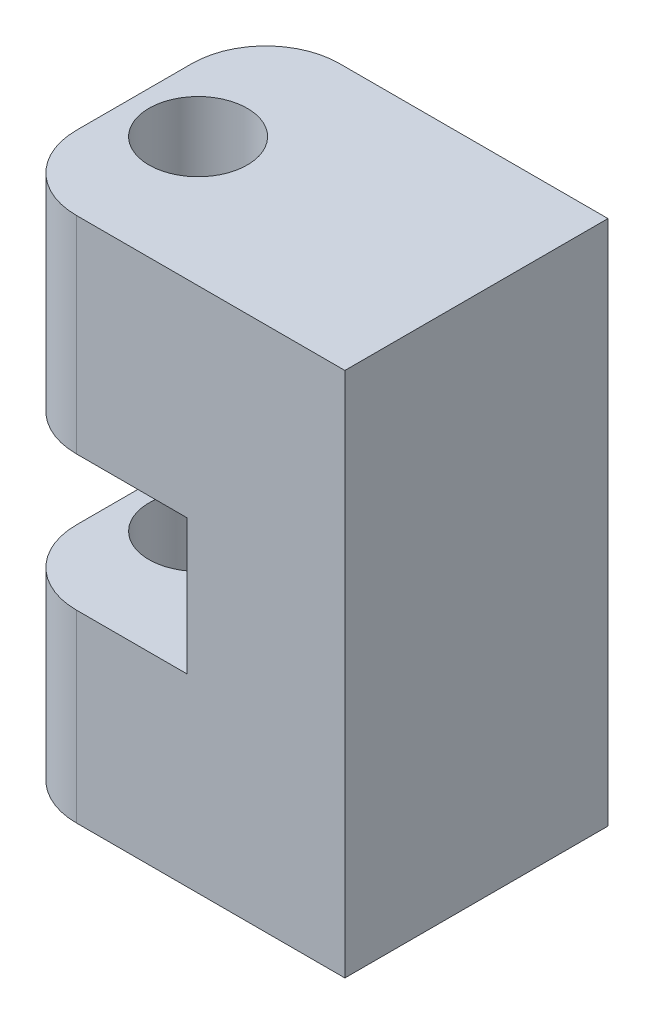
SolidWorks part; units mm, degrees
ref_plane "Front" through (0, 0, 0) normal (0, 0, 1) x (1, 0, 0)
ref_plane "Top" through (0, 0, 0) normal (0, 1, 0) x (1, 0, 0)
ref_plane "Right" through (0, 0, 0) normal (1, 0, 0) x (0, 0, -1)
sketch "Sketch1" plane through (0, 0, 0) normal (0, 1, 0) x (1, 0, 0)
  line L0 (0, 9.3172) -> (0, 9.1678) construction
  line L1 (0, 0) -> (20.32, 0)
  line L2 (0, 0) -> (0, 12.7)
  line L3 (0, 12.7) -> (20.32, 12.7)
  line L4 (20.32, 0) -> (20.32, 12.7)
  line L5 (0.0894, 9.3172) -> (0.0894, 9.1678)
  line L6 (-0.0894, 9.3172) -> (-0.0894, 9.1678)
  line L7 (0, 7.6957) -> (0, 5.0493) construction
  line L10 (5.1, 7.6957) -> (5.1, 5.0493)
  line L11 (-5.1, 7.6957) -> (-5.1, 5.0493)
  arc A0 (0.0894, 9.3172) -> (-0.0894, 9.3172) centre (0, 9.3172) ccw
  arc A1 (-0.0894, 9.1678) -> (0.0894, 9.1678) centre (0, 9.1678) ccw
  arc A4 (5.1, 7.6957) -> (-5.1, 7.6957) centre (0, 7.6957) ccw
  arc A5 (-5.1, 5.0493) -> (5.1, 5.0493) centre (0, 5.0493) ccw
  point P7 (0, 9.2425)
  point P14 (0, 6.3725)
  dimension "D1" = 20.32
  dimension "D2" = 12.7
extrude "Boss-Extrude4" add sketch "Sketch1" along normal blind 25.4 contours L11 A5 L1 L2 A1 L6 A0 L3 A4 | L1 A5 L10 A4 L3 L2 A0 L5 A1 | A5 L1 L4 L3 A4 L10 region at (2.2644, 0, -6.3666) region at (-2.2571, 0, -6.3757) region at (12.2627, 0, -6.3452)
sketch "Sketch3" plane through (0, 25.4, 0) normal (0, 1, 0) x (1, 0, 0)
  circle A0 centre (0, 6.1634) radius 2
  dimension "D1" = 4
extrude "Cut-Extrude1" cut sketch "Sketch3" against normal blind 25.4 contours A0
sketch "Sketch5" plane through (20.32, 0, 0) normal (1, 0, 0) x (0, 0, -1)
  line L1 (38.2751, 38.8271) -> (-16.024, 38.8271)
  line L2 (38.2751, 38.8271) -> (38.2751, -55.3885)
  line L3 (38.2751, -55.3885) -> (-16.024, -55.3885)
  line L4 (-16.024, 38.8271) -> (-16.024, -55.3885)
extrude "Cut-Extrude2" cut sketch "Sketch5" against normal blind 4.5
sketch "Sketch7" plane through (-5.1, 0, 0) normal (-1, 0, 0) x (0, 0, 1)
  line L0 (-7.6957, 25.4) -> (-5.0493, 25.4) construction
  line L1 (-15.6651, 15) -> (3.0281, 15)
  line L2 (-15.6651, 15) -> (-15.6651, 9.5)
  line L3 (-15.6651, 9.5) -> (3.0281, 9.5)
  line L4 (3.0281, 15) -> (3.0281, 9.5)
  dimension "D1" = 5.5
  dimension "D2" = 10.4
extrude "Cut-Extrude3" cut sketch "Sketch7" against normal blind 14.5
sketch "Sketch9" plane through (0, 0, -12.7) normal (0, 0, -1) x (-1, 0, 0)
  line L1 (-22.5674, 28.7595) -> (13.5442, 28.7595)
  line L2 (-22.5674, 28.7595) -> (-22.5674, -4.4046)
  line L3 (-22.5674, -4.4046) -> (13.5442, -4.4046)
  line L4 (13.5442, 28.7595) -> (13.5442, -4.4046)
extrude "Cut-Extrude4" cut sketch "Sketch9" against normal blind 1
sketch "Sketch10" plane through (0, 0, 0) normal (0, 0, 1) x (1, 0, 0)
  line L1 (-28.2632, -7.6451) -> (34.5285, -7.6451)
  line L2 (-28.2632, -7.6451) -> (-28.2632, 29.5981)
  line L3 (-28.2632, 29.5981) -> (34.5285, 29.5981)
  line L4 (34.5285, -7.6451) -> (34.5285, 29.5981)
extrude "Cut-Extrude6" cut sketch "Sketch10" against normal blind 1
fillet "Fillet2" radius 3 4 edges at (-3.1005, 4.75, -1) (-3.1005, 20.2, -1) (-3.1585, 20.2, -11.7) (-3.1585, 4.75, -11.7)
sketch "Sketch11" plane through (9.4, 0, 0) normal (-1, 0, 0) x (0, 0, 1)
  line L1 (-11.7, 9.5) -> (-1, 9.5)
  line L2 (-11.7, 9.5) -> (-11.7, 15)
  line L3 (-11.7, 15) -> (-1, 15)
  line L4 (-1, 9.5) -> (-1, 15)
extrude "Boss-Extrude5" add sketch "Sketch11" along normal blind 2
sketch "Sketch12" plane through (-5.1, 0, 0) normal (-1, 0, 0) x (0, 0, 1)
  line L1 (-13.4183, -11.6019) -> (0, -11.6019)
  line L2 (-13.4183, -11.6019) -> (-13.4183, 44.9502)
  line L3 (-13.4183, 44.9502) -> (0, 44.9502)
  line L4 (0, -11.6019) -> (0, 44.9502)
extrude "Cut-Extrude7" cut sketch "Sketch12" against normal blind 10
sketch "Sketch14" plane through (7.4, 0, 0) normal (-1, 0, 0) x (0, 0, 1)
  line L1 (-11.7, 9.5) -> (-1, 9.5)
  line L2 (-11.7, 9.5) -> (-11.7, 15)
  line L3 (-11.7, 15) -> (-1, 15)
  line L4 (-1, 9.5) -> (-1, 15)
extrude "Boss-Extrude7" add sketch "Sketch14" along normal blind 2
sketch "Sketch15" plane through (4.9, 0, 0) normal (-1, 0, 0) x (0, 0, 1)
  line L1 (-11.7, 0) -> (-1, 0)
  line L2 (-11.7, 0) -> (-11.7, 9.5)
  line L3 (-11.7, 9.5) -> (-1, 9.5)
  line L4 (-1, 0) -> (-1, 9.5)
extrude "Boss-Extrude8" add sketch "Sketch15" along normal blind 6
sketch "Sketch16" plane through (4.9, 0, 0) normal (-1, 0, 0) x (0, 0, 1)
  line L1 (-11.7, 15) -> (-1, 15)
  line L2 (-11.7, 15) -> (-11.7, 25.4)
  line L3 (-11.7, 25.4) -> (-1, 25.4)
  line L4 (-1, 15) -> (-1, 25.4)
extrude "Boss-Extrude9" add sketch "Sketch16" along normal blind 6
fillet "Fillet3" radius 3 4 edges at (-1.1, 20.2, -1) (-1.1, 20.2, -11.7) (-1.1, 4.75, -11.7) (-1.1, 4.75, -1)
sketch "Sketch18" plane through (5.4, 0, 0) normal (-1, 0, 0) x (0, 0, 1)
  line L1 (-11.7, 15) -> (-1, 15)
  line L2 (-11.7, 15) -> (-11.7, 9.5)
  line L3 (-11.7, 9.5) -> (-1, 9.5)
  line L4 (-1, 15) -> (-1, 9.5)
extrude "Cut-Extrude8" cut sketch "Sketch18" against normal blind 1
sketch "Sketch21" plane through (15.82, 0, 0) normal (1, 0, 0) x (0, 0, -1)
  line L1 (-13.6512, 30.6954) -> (22.1459, 30.6954)
  line L2 (-13.6512, 30.6954) -> (-13.6512, -4.5948)
  line L3 (-13.6512, -4.5948) -> (22.1459, -4.5948)
  line L4 (22.1459, 30.6954) -> (22.1459, -4.5948)
extrude "Cut-Extrude9" cut sketch "Sketch21" against normal blind 3
sketch "Sketch22" plane through (0, 25.4, 0) normal (0, 1, 0) x (1, 0, 0)
  line L1 (-8.3333, 22.5284) -> (17.604, 22.5284)
  line L2 (-8.3333, 22.5284) -> (-8.3333, -13.9298)
  line L3 (-8.3333, -13.9298) -> (17.604, -13.9298)
  line L4 (17.604, 22.5284) -> (17.604, -13.9298)
extrude "Cut-Extrude10" cut sketch "Sketch22" against normal blind 2
sketch "Sketch23" plane through (0, 0, 0) normal (0, -1, 0) x (1, 0, 0)
  line L1 (-6.2486, 12.1341) -> (24.9701, 12.1341)
  line L2 (-6.2486, 12.1341) -> (-6.2486, -25.7385)
  line L3 (-6.2486, -25.7385) -> (24.9701, -25.7385)
  line L4 (24.9701, 12.1341) -> (24.9701, -25.7385)
extrude "Cut-Extrude11" cut sketch "Sketch23" against normal blind 2
sketch "Sketch24" plane through (0, 2, 0) normal (0, -1, 0) x (1, 0, 0)
  line L0 (-1.1, -4) -> (-1.1, -8.7) construction
  line L2 (12.82, -1) -> (1.9, -1) construction
  circle A0 centre (1.6, -6.25) radius 2
  point P6 (2.5117, -1)
  point P7 (0, 0)
  dimension "D1" = 4
  dimension "D2" = 2.7
  dimension "D3" = 5.25
extrude "Cut-Extrude12" cut sketch "Sketch24" against normal blind 24
